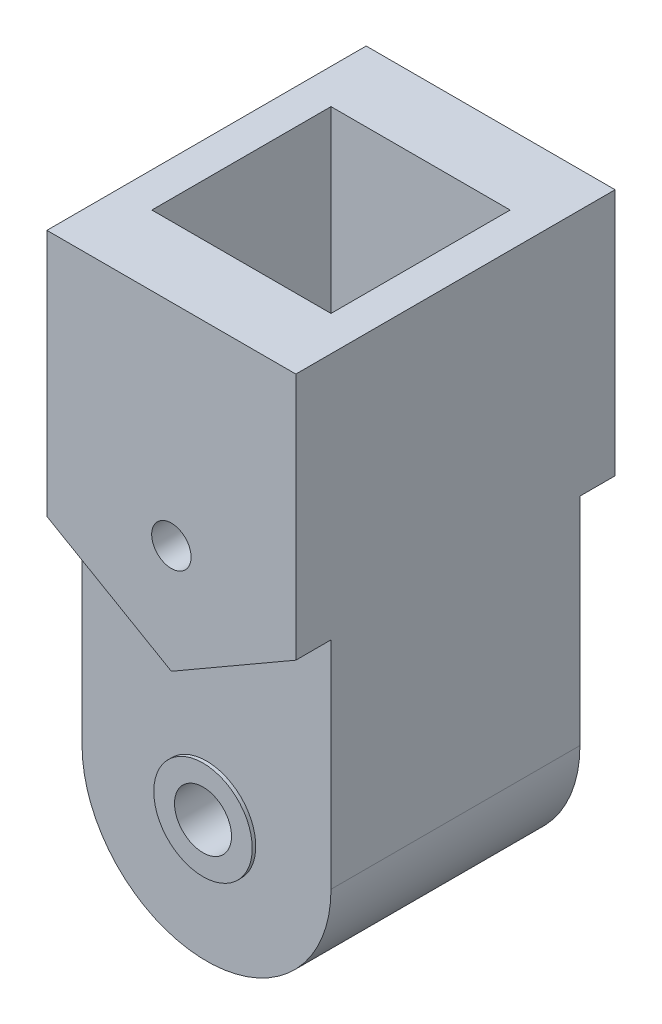
SolidWorks part; units mm, degrees
material "PETG"
ref_plane "Front Plane" through (0, 0, 0) normal (0, 0, 1) x (1, 0, 0)
ref_plane "Top Plane" through (0, 0, 0) normal (0, 1, 0) x (1, 0, 0)
ref_plane "Right Plane" through (0, 0, 0) normal (1, 0, 0) x (0, 0, -1)
sketch "Sketch1" plane through (0, 0, 0) normal (0, 1, 0) x (1, 0, 0)
  line L1 (-12.7375, -12.7375) -> (12.7375, -12.7375)
  line L2 (-12.7375, -12.7375) -> (-12.7375, 12.7375)
  line L3 (-12.7375, 12.7375) -> (12.7375, 12.7375)
  line L4 (12.7375, -12.7375) -> (12.7375, 12.7375)
  line L5 (-17.7, -17.7) -> (17.7, -17.7)
  line L6 (-17.7, -17.7) -> (-17.7, 17.7)
  line L7 (-17.7, 17.7) -> (17.7, 17.7)
  line L8 (17.7, -17.7) -> (17.7, 17.7)
  point P8 (0, -17.7)
  point P9 (0, -12.7375)
  point P12 (-17.7, 0)
  point P13 (-12.7375, 0)
  dimension "D1" = 25.475
  dimension "D2" = 35.4
extrude "Boss-Extrude1" add sketch "Sketch1" along normal blind 50.0375
extrude "Boss-Extrude2" add sketch "Sketch1<3>" against normal blind 9.9625 contours L1 L4 L3 L2 | L5 L8 L7 L6 L4 L1 L2 L3 region at (0, 0, 0) region at (-17.1994, 0, 0)
sketch "Sketch1<3>" plane through (0, 0, 0) normal (0, 1, 0) x (1, 0, 0) same geometry as "Sketch1"
sketch "Sketch2" plane through (0, 0, -17.7) normal (0, 0, 1) x (1, 0, 0)
  line L1 (17.7, 50.0375) -> (17.7, -9.9625) construction
  line L4 (-17.7, -9.9625) -> (17.7, -9.9625) construction
  line L5 (-17.7, -15.9125) -> (-17.7, -9.9625)
  line L6 (17.7, -9.9625) -> (17.7, -15.9125)
  line L7 (17.7, -9.9625) -> (-17.7, -9.9625)
  circle A0 centre (0, -15.9625) radius 4.05
  circle A2 centre (0, -15.9625) radius 11 construction
  arc A3 (17.7, -15.9125) -> (-17.7, -15.9125) centre (0, -15.9125) cw
  point P3 (0, 0)
  point P4 (0, 0)
  point P5 (-17.7, -16.4965)
  dimension "D1" = 8.1
  dimension "D3" = 22
  dimension "D2" = 6
  dimension "D4" = 5.95
extrude "Boss-Extrude5" add sketch "Sketch2" along normal up to surface (35.4 mm away) up to face at (0, 20.0375, 17.7)
ref_plane "Plane1" through (0, -33.6125, 0) normal (0, -1, 0) x (-1, 0, 0)
sketch "Sketch3" plane through (0, -33.6125, 0) normal (0, -1, 0) x (-1, 0, 0)
  circle A0 centre (0, 0) radius 3.15
  dimension "D1" = 6.3
extrude "Cut-Extrude1" cut sketch "Sketch3" against normal through all
sketch "Sketch4" plane through (0, -33.6125, 0) normal (0, -1, 0) x (-1, 0, 0)
  circle A0 centre (0, 0) radius 5.5
  dimension "D1" = 11
extrude "Cut-Extrude2" cut sketch "Sketch4" against normal offset from surface (25.6125 mm away) 8 up to face at (0, 0, 3.15)
sketch "Sketch5" plane through (0, 0, 17.7) normal (0, 0, 1) x (1, 0, 0)
  circle A0 centre (0, -15.9625) radius 7
  circle A1 centre (0, -15.9625) radius 4.05 construction
  circle M6 centre (0, -15.9625) radius 4.05
  dimension "D1" = 14
extrude "Boss-Extrude6" add sketch "Sketch5" along normal blind 0.5 contours A0 M6 region at (-6.802, -15.9625, 17.7)
mirror "Mirror1" about plane through (0, 0, 0) normal (0, 0, 1) of "Boss-Extrude6"
sketch "Sketch6" plane through (0, 0, 17.7) normal (0, 0, 1) x (1, 0, 0)
  line L5 (8.875, -31.2845) -> (52.1763, -6.2845) construction
  line L6 (-8.875, -0.5405) -> (34.4263, 24.4595) construction
  line L7 (52.1763, -6.2845) -> (34.4263, 24.4595) construction
  line L8 (0, -16) -> (0, -79.4793) construction
  line L9 (17.7, 50.0375) -> (17.7, -15.9125) construction
  line L10 (17.7, 14.8025) -> (-17.7, 14.8025)
  line L11 (17.7, 14.8025) -> (17.7, 50.0375)
  line L12 (17.7, 50.0375) -> (-17.7, 50.0375)
  line L13 (-17.7, 14.8025) -> (-17.7, 50.0375)
  line L14 (17.7, 14.8025) -> (0, 4.5834)
  line L15 (0, 4.5834) -> (-17.7, 14.8025)
  circle A1 centre (0, -15.9125) radius 17.75
  arc A2 (-17.7, -15.9125) -> (17.7, -15.9125) centre (0, -15.9125) ccw construction
  line M4 (-17.7, 50.0375) -> (-17.7, -15.9125)
  line M6 (17.7, -15.9125) -> (17.7, 50.0375)
  line M7 (17.7, 50.0375) -> (-17.7, 50.0375)
  dimension "D1" = 50
  dimension "D2" = 120
  dimension "D3" = 35.5
extrude "Boss-Extrude7" add sketch "Sketch6" along normal blind 5 contours L14 L10 M4 | L10 M6 M7 M4 region at (0, 11.3962, 17.7) region at (0, 32.42, 17.7)
sketch "Sketch7" plane through (0, 0, 22.7) normal (0, 0, 1) x (1, 0, 0)
  line L0 (17.7, 50.0375) -> (-17.7, 50.0375) construction
  line L1 (17.7, 20.0375) -> (0, 20.0375) construction
  line L2 (17.7, 14.8025) -> (17.7, 50.0375) construction
  line L3 (0, 20.0375) -> (-17.7, 20.0375) construction
  line L4 (-17.7, 50.0375) -> (-17.7, 14.8025) construction
  circle A0 centre (0, 20.0375) radius 2.8
  dimension "D1" = 30
  dimension "D2" = 5.6
extrude "Cut-Extrude3" cut sketch "Sketch7" against normal up to next
mirror "Mirror2" about plane through (0, 0, 0) normal (0, 0, 1) of "Boss-Extrude7", "Cut-Extrude3"
equation "\"tol_dia_id_intfc\" = 0.0500mm ' For hole diameters - Interference fit"
equation "\"tol_dia_id_slip\"  = 0.0750mm ' For hole diameters - Slip fit"
equation "\"tol_dia_id_clear\" = 0.1000mm ' For hole diameters - Clearance fit"
equation "\"tol_dia_od_intfc\" = 0.0500mm ' For shaft diameters - Interference fit"
equation "\"tol_dia_od_slip\"  = 0.0750mm ' For shaft diameters - Slip fit"
equation "\"tol_dia_od_clear\" = 0.1000mm ' For shaft diameters - Clearance fit"
equation "\"tol_general_intfc\"= 0.0250mm ' For general parts (Horiz) - Interference fit"
equation "\"tol_general_slip\" = 0.0375mm ' For general parts (Horiz) - Slip fit"
equation "\"tol_general_clear\"= 0.0500mm ' For general parts (Horiz) - Clearance fit"
equation "\"tol_layer_intfc\"  = 0.0250mm ' For all parts (Vert) - Interference fit"
equation "\"tol_layer_slip\"   = 0.0375mm ' For all parts (Vert) - Slip fit"
equation "\"tol_layer_clear\"  = 0.0500mm ' For all parts (Vert) - Clearance fit"
equation "\"tol_corner_rad\"   = 0.100mm ' For corners that fit into other parts"
equation "\"D1@Sketch1\"=25.40mm+\"tol_general_slip\"*2"
equation "\"D2@Sketch1\"=25.4+10"
equation "\"D1@Boss-Extrude1\"= 50.00mm + \"tol_layer_slip\""
equation "\"D1@Boss-Extrude2\"=10.00mm-\"tol_layer_slip\""
equation "\"D1@Sketch2\"=8.00mm+\"tol_dia_id_clear\""
equation "\"D4@Sketch2\"=6.00mm-\"tol_dia_od_clear\"/2"
equation "\"D3@Sketch6\"=25.4+10+\"tol_general_clear\"*2"
